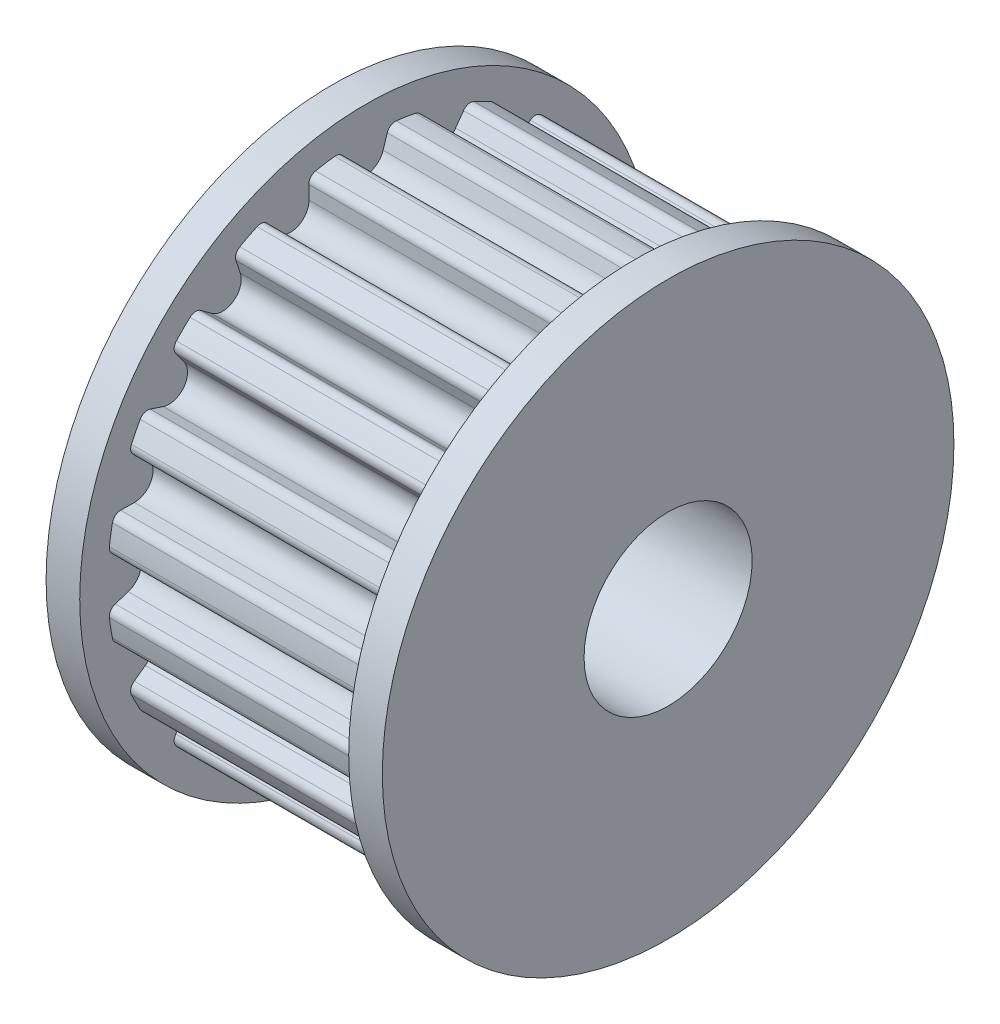
SolidWorks part; units mm, degrees
ref_plane "前视基准面" through (0, 0, 0) normal (0, 0, 1) x (1, 0, 0)
ref_plane "上视基准面" through (0, 0, 0) normal (0, 1, 0) x (1, 0, 0)
ref_plane "右视基准面" through (0, 0, 0) normal (1, 0, 0) x (0, 0, -1)
sketch "草图1" plane through (0, 0, 0) normal (0, 0, 1) x (1, 0, 0)
  line L0 (0, 0) -> (64.8368, 0) construction
  line L1 (0, 5) -> (0, 15.345)
  line L2 (0, 15.345) -> (16, 15.345)
  line L3 (16, 15.345) -> (16, 5)
  line L6 (16, 5) -> (0, 5)
  dimension "d" = 10
  dimension "da" = 30.69
  dimension "D1" = 16
revolve "旋转1" add sketch "草图1" angle 360 about L0
sketch "草图4" plane through (0, 0, 0) normal (-1, 0, 0) x (0, 0, 1)
  line L0 (0, 6) -> (0, 0) construction
  line L1 (-1, 4.899) -> (1, 4.899)
  line L2 (-1, 4.899) -> (-1, 6)
  line L3 (-1, 6) -> (1, 6)
  line L4 (1, 4.899) -> (1, 6)
  circle A1 centre (0, 0) radius 5 construction
  point P6 (0, 6)
  dimension "键槽高度" = 6
  dimension "键槽宽度" = 2
  dimension "t1" = 1
extrude "切除-拉伸1" cut sketch "草图4" against normal through all
sketch "草图6" plane through (0, 0, 0) normal (1, 0, 0) x (0, 0, -1)
  line L0 (0, 0) -> (0, 30.6512) construction
  line L1 (1.2935, 14.8894) -> (1.0491, 14.1142)
  line L2 (2.3254, 15.1678) -> (2.8106, 16.7067)
  line L3 (-2.3254, 15.1678) -> (-2.8106, 16.7067)
  line L4 (-1.2935, 14.8894) -> (-1.0491, 14.1142)
  circle A0 centre (0, 0) radius 15.345 construction
  circle A1 centre (0, 0) radius 13.345 construction
  arc A2 (-1.0491, 14.1142) -> (1.0491, 14.1142) centre (0, 14.445) ccw
  arc A3 (2.8106, 16.7067) -> (-2.8106, 16.7067) centre (0, 0) ccw
  arc A4 (1.2935, 14.8894) -> (1.83, 15.2355) centre (1.7704, 14.7391) cw
  arc A5 (1.83, 15.2355) -> (2.3254, 15.1678) centre (0, 0) cw
  arc A6 (-1.83, 15.2355) -> (-2.3254, 15.1678) centre (0, 0) ccw
  arc A7 (-1.2935, 14.8894) -> (-1.83, 15.2355) centre (-1.7704, 14.7391) ccw
  point P7 (0, 4.8294)
  point P8 (0, 28.6512)
  point P15 (1.4165, 15.2795)
  dimension "D1" = 26.69
  dimension "ra" = 0.5
  dimension "rf" = 1.1
  dimension "hg" = 2
  dimension "D3" = 0.5
  dimension "D4" = 1.6136
  dimension "angle" = 35
  dimension "bw" = 4.8294
extrude "切除-拉伸2" cut sketch "草图6" along normal up to next
ref_axis "基准轴1" through (-1.4, 0, 0) along (1, 0, 0)
pattern_circular "阵列(圆周)3" count 20 over 360 about axis through (-1.4, 0, 0) along (1, 0, 0) of "切除-拉伸2"
sketch "草图7" plane through (0, 0, 0) normal (-1, 0, 0) x (0, 0, 1)
  line L0 (-1, 6) -> (-1, 4.899) construction
  line L1 (1, 6) -> (-1, 6) construction
  line L2 (1, 4.899) -> (1, 6) construction
  line L3 (-1, 6) -> (-1, 4.899)
  line L4 (1, 6) -> (-1, 6)
  line L5 (1, 4.899) -> (1, 6)
  circle A0 centre (0, 0) radius 17
  arc A1 (-1, 4.899) -> (1, 4.899) centre (0, 0) ccw construction
  arc A2 (-1, 4.899) -> (1, 4.899) centre (0, 0) ccw
  dimension "D1" = 34
extrude "凸台-拉伸1" add sketch "草图7" along normal blind 2
sketch "草图8" plane through (16, 0, 0) normal (1, 0, 0) x (0, 0, -1)
  line L0 (1, 6) -> (1, 4.899) construction
  line L1 (-1, 6) -> (1, 6) construction
  line L2 (-1, 4.899) -> (-1, 6) construction
  line L3 (1, 6) -> (1, 4.899)
  line L4 (-1, 6) -> (1, 6)
  line L5 (-1, 4.899) -> (-1, 6)
  circle A0 centre (0, 0) radius 17
  arc A1 (-1, 4.899) -> (1, 4.899) centre (0, 0) ccw construction
  arc A2 (-1, 4.899) -> (1, 4.899) centre (0, 0) ccw
  dimension "D1" = 34
extrude "凸台-拉伸2" add sketch "草图8" along normal blind 2
sketch "草图9" plane through (18, 0, 0) normal (1, 0, 0) x (0, 0, -1)
  line L0 (-1, 4.899) -> (-1, 6)
  line L1 (-1, 6) -> (1, 6)
  line L2 (1, 6) -> (1, 4.899)
  arc A0 (1, 4.899) -> (-1, 4.899) centre (0, 0) ccw
extrude "凸台-拉伸3" add sketch "草图9" against normal up to surface (20 mm away) up to face at (-2, 0, 17)
equation "\"键槽高度@草图4\" = \"d@草图1\" / 2  + \"t1@草图4\""
equation "\"D1@草图6\" = \"da@草图1\"  - \"hg@草图6\" - \"hg@草图6\""
equation "\"D3@草图6\" = \"ra@草图6\""
